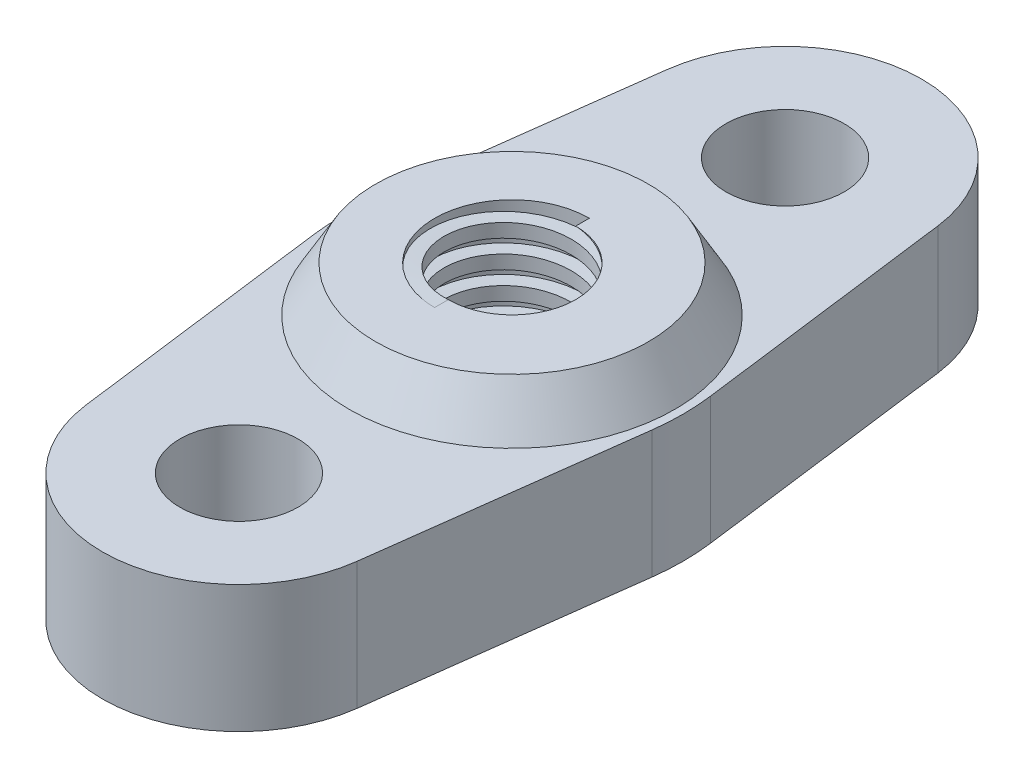
SolidWorks part; units mm, degrees
ref_plane "Front Plane" through (0, 0, 0) normal (0, 0, 1) x (1, 0, 0)
ref_plane "Top Plane" through (0, 0, 0) normal (0, 1, 0) x (1, 0, 0)
ref_plane "Right Plane" through (0, 0, 0) normal (1, 0, 0) x (0, 0, -1)
sketch "Sketch3" plane through (0, 0, 0) normal (0, 0, 1) x (1, 0, 0)
  line L0 (0, 60.6771) -> (0, -34.8406) construction
  line L1 (14, 38) -> (14, 0)
  line L2 (14, 0) -> (90, 0)
  line L3 (90, 0) -> (90, 28)
  line L4 (90, 28) -> (35.7735, 28)
  line L5 (35.7735, 28) -> (30, 38)
  line L6 (30, 38) -> (14, 38)
  dimension "D1" = 28
  dimension "D2" = 90
  dimension "D3" = 10
  dimension "D4" = 30
  dimension "D5" = 14
revolve "Revolve1" add sketch "Sketch3" angle 360 about L0
sketch "Sketch4" plane through (0, 28, 0) normal (0, 1, 0) x (1, 0, 0)
  line L0 (0, 60) -> (0, -60) construction
  line L1 (-75.3825, 0) -> (90, 0) construction
  line L2 (-29.7528, 63.8434) -> (-38, 0)
  line L3 (-29.7528, -63.8434) -> (-38, 0)
  line L4 (29.7528, 63.8434) -> (38, 0)
  line L5 (38, 0) -> (29.7528, -63.8434)
  arc A2 (29.7528, 63.8434) -> (-29.7528, 63.8434) centre (0, 60) ccw
  arc A3 (-29.7528, -63.8434) -> (29.7528, -63.8434) centre (0, -60) ccw
  circle A4 centre (0, -60) radius 13
  circle A5 centre (0, 60) radius 13
  circle A6 centre (0, 0) radius 90 construction
  circle M3 centre (0, 0) radius 90
  dimension "D2" = 60
  dimension "D3" = 60
  dimension "D4" = 26
  dimension "D5" = 26
  dimension "D1" = 60
  dimension "D6" = 76
  dimension "D7" = 60
extrude "Cut-Extrude1" cut sketch "Sketch4" against normal through all contours A3 L3 L2 A2 M3 | A3 A2 L4 L5 M3 | A4 | A5
fillet "Fillet1" radius 50 2 edges at (-38, 14, 0) (38, 14, 0)
sketch "Sketch5" plane through (0, 38, 0) normal (0, 1, 0) x (1, 0, 0)
  circle A0 centre (0, 0) radius 17
  dimension "D1" = 34
curve "Helix/Spiral1" pitch 6 height 50 turns 8.3333
sketch "Sketch6" plane through (0, 0, 0) normal (1, 0, 0) x (0, 0, -1)
  line L1 (-17, 41) -> (-14, 41)
  line L2 (-17, 41) -> (-17, 38)
  line L3 (-17, 38) -> (-14, 38)
  line L4 (-14, 41) -> (-14, 38)
  line L5 (-17, 41) -> (-14, 38) construction
  line L6 (-17, 38) -> (-14, 41) construction
  point P0 (-15.5, 39.5)
  dimension "D1" = 3
  dimension "D2" = 3
sweep "Cut-Sweep1" cut profiles "Sketch6" path "Helix/Spiral1"
